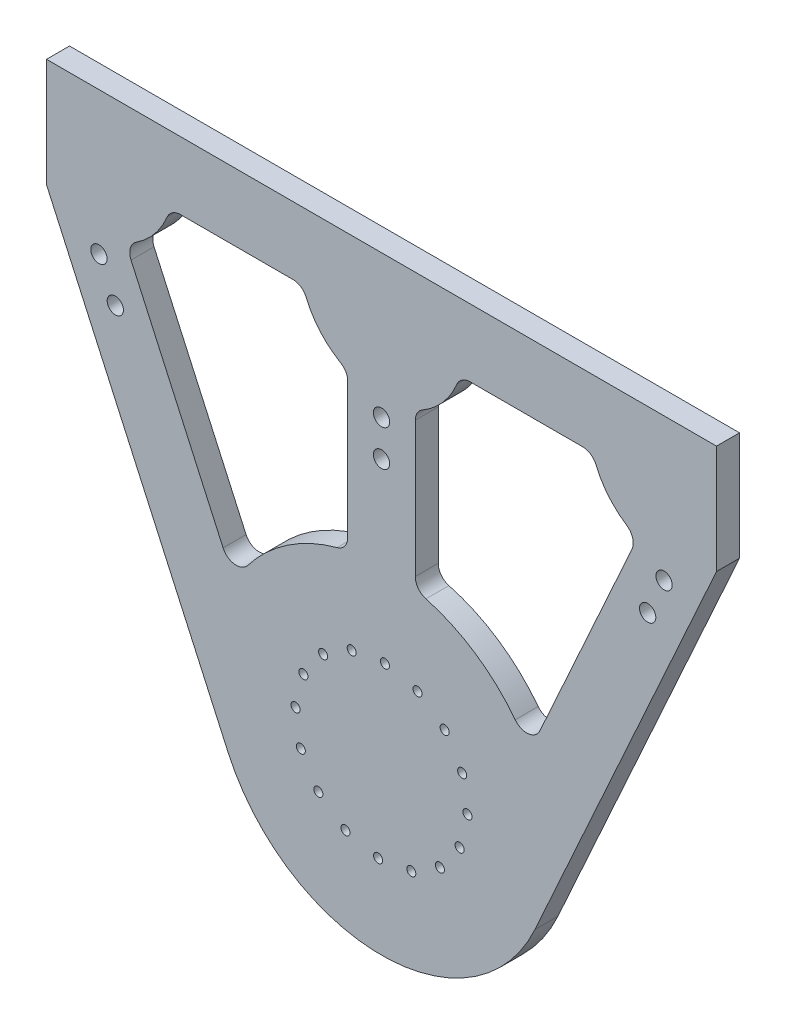
SolidWorks part; units mm, degrees
ref_plane "Front Plane" through (0, 0, 0) normal (0, 0, 1) x (1, 0, 0)
ref_plane "Top Plane" through (0, 0, 0) normal (0, 1, 0) x (1, 0, 0)
ref_plane "Right Plane" through (0, 0, 0) normal (1, 0, 0) x (0, 0, -1)
sketch "Sketch1" plane through (0, 0, 0) normal (0, 0, 1) x (1, 0, 0)
  line L1 (92.5, 121.5) -> (-92.5, 121.5)
  line L3 (0, 0) -> (0, 121.5) construction
  line L4 (-92.5, 121.5) -> (-92.5, 91.5)
  line L5 (-92.5, 91.5) -> (-42.3564, -19.1882)
  line L6 (92.5, 121.5) -> (92.5, 91.5)
  line L7 (92.5, 91.5) -> (42.3564, -19.1882)
  line L8 (42.3564, -19.1882) -> (-42.3564, -19.1882) construction
  circle A0 centre (0, 0) radius 46.5 construction
  arc A1 (-42.3564, -19.1882) -> (42.3564, -19.1882) centre (0, 0) ccw
  dimension "D1" = 93
  dimension "D2" = 185
  dimension "D3" = 121.5
  dimension "D4" = 30
extrude "Boss-Extrude1" add sketch "Sketch1" along normal mid plane 6.35
sketch "Sketch3" plane through (0, 0, -3.175) normal (0, 0, -1) x (-1, 0, 0)
  circle A0 centre (17.4402, -16.1215) radius 1.25 construction
  circle A1 centre (22.282, -8.2203) radius 1.25 construction
  circle A2 centre (9.9432, -21.5684) radius 1.25 construction
  circle A3 centre (0.9324, -23.7317) radius 1.25 construction
  circle A4 centre (-8.2203, -22.282) radius 1.25 construction
  circle A5 centre (-16.1215, -17.4402) radius 1.25 construction
  circle A6 centre (-21.5684, -9.9432) radius 1.25 construction
  circle A7 centre (-23.7317, -0.9324) radius 1.25 construction
  circle A8 centre (-22.282, 8.2203) radius 1.25 construction
  circle A9 centre (-17.4402, 16.1215) radius 1.25 construction
  circle A10 centre (-9.9432, 21.5684) radius 1.25 construction
  circle A11 centre (-0.9324, 23.7317) radius 1.25 construction
  circle A12 centre (8.2203, 22.282) radius 1.25 construction
  circle A13 centre (16.1215, 17.4402) radius 1.25 construction
  circle A14 centre (21.5684, 9.9432) radius 1.25 construction
  circle A15 centre (23.7317, 0.9324) radius 1.25 construction
  circle A16 centre (17.4402, -16.1215) radius 1.25
  circle A17 centre (22.282, -8.2203) radius 1.25
  circle A18 centre (9.9432, -21.5684) radius 1.25
  circle A19 centre (0.9324, -23.7317) radius 1.25
  circle A20 centre (-8.2203, -22.282) radius 1.25
  circle A21 centre (-16.1215, -17.4402) radius 1.25
  circle A22 centre (-21.5684, -9.9432) radius 1.25
  circle A23 centre (-23.7317, -0.9324) radius 1.25
  circle A24 centre (-22.282, 8.2203) radius 1.25
  circle A25 centre (-17.4402, 16.1215) radius 1.25
  circle A26 centre (-9.9432, 21.5684) radius 1.25
  circle A27 centre (-0.9324, 23.7317) radius 1.25
  circle A28 centre (8.2203, 22.282) radius 1.25
  circle A29 centre (16.1215, 17.4402) radius 1.25
  circle A30 centre (21.5684, 9.9432) radius 1.25
  circle A31 centre (23.7317, 0.9324) radius 1.25
extrude "Cut-Extrude2" cut sketch "Sketch3" against normal through all both and the other way through all
ref_plane "Plane1" through (0, 91.5, 0) normal (0, 1, 0) x (1, 0, 0)
ref_plane "Plane2" through (0, 106.5, 0) normal (0, 1, 0) x (1, 0, 0)
sketch "Sketch6" plane through (0, 0, -3.175) normal (0, 0, -1) x (-1, 0, 0)
  line L0 (0, 0) -> (0, 121.5) construction
  line L1 (-92.5, 121.5) -> (-77.5, 121.5) construction
  line L2 (-92.5, 121.5) -> (-92.5, 91.5) construction
  line L3 (-92.5, 91.5) -> (-77.5, 91.5) construction
  line L4 (-77.5, 121.5) -> (-77.5, 91.5) construction
  line L5 (-92.5, 121.5) -> (92.5, 121.5) construction
  line L6 (-85, 121.5) -> (-85, 106.5) construction
  line L11 (-77.5, 106.5) -> (-92.5, 106.5) construction
  line L12 (-7.5, 121.5) -> (7.5, 121.5) construction
  line L13 (-7.5, 121.5) -> (-7.5, 91.5) construction
  line L14 (-7.5, 91.5) -> (7.5, 91.5) construction
  line L15 (7.5, 121.5) -> (7.5, 91.5) construction
  line L16 (-85, 91.5) -> (-85, 106.5) construction
  circle A0 centre (-85, 114) radius 2.25
  circle A1 centre (-85, 99) radius 2.25
  circle A2 centre (0, 114) radius 2.25
  circle A3 centre (0, 99) radius 2.25
  circle A6 centre (85, 114) radius 2.25
  circle A7 centre (85, 99) radius 2.25
  point P18 (0, 121.5)
  point P35 (-85, 114)
  point P38 (-85, 99)
  dimension "D3" = 4.5
  dimension "D1" = 30
  dimension "D2" = 15
sketch "Sketch12" plane through (0, 0, -3.175) normal (0, 0, -1) x (-1, 0, 0)
  line L0 (0, -46.5) -> (0, 121.5) construction
  line L1 (-92.5, 121.5) -> (92.5, 121.5) construction
  line L2 (-87, 116) -> (-92.5, 116) construction
  line L3 (-87, 116) -> (-73, 116) construction
  line L4 (-87, 116) -> (-87, 102) construction
  line L5 (-87, 102) -> (-73, 102) construction
  line L6 (-73, 116) -> (-73, 102) construction
  line L7 (-92.5, 91.5) -> (-92.5, 121.5) construction
  line L8 (-87, 116) -> (-87, 121.5) construction
  line L9 (12.5, 121.5) -> (-12.5, 121.5) construction
  line L11 (-7, 102) -> (7, 102) construction
  line L12 (-7, 102) -> (-7, 116) construction
  line L13 (-7, 116) -> (7, 116) construction
  line L14 (7, 102) -> (7, 116) construction
  circle A0 centre (-7, 102) radius 2.25
  circle A2 centre (7, 102) radius 2.25
  circle A4 centre (7, 116) radius 2.25
  circle A5 centre (-87, 116) radius 2.25
  circle A6 centre (-73, 116) radius 2.25
  circle A7 centre (-73, 102) radius 2.25
  circle A8 centre (-87, 102) radius 2.25
  arc A9 (-42.3564, -19.1882) -> (42.3564, -19.1882) centre (0, 0) ccw construction
  circle A10 centre (87, 102) radius 2.25
  circle A11 centre (73, 102) radius 2.25
  circle A12 centre (73, 116) radius 2.25
  circle A13 centre (87, 116) radius 2.25
  circle A14 centre (-7, 116) radius 2.25
  point P22 (-87, 109)
  point P23 (-7, 109)
  point P24 (0, 116)
  dimension "D3" = 4.5
  dimension "D1" = 5.5
  dimension "D2" = 14
extrude "Cut-Extrude6" cut sketch "Sketch12" against normal through all both and the other way through all
sketch "Sketch13" plane through (0, 0, -3.175) normal (0, 0, -1) x (-1, 0, 0)
  line L0 (-40.7392, 22.418) -> (-70.6842, 88.5191)
  line L1 (40.7392, 22.418) -> (70.6842, 88.5191)
  line L2 (-9.3209, 88.5215) -> (-9.3209, 45.5562)
  line L3 (9.3209, 88.5215) -> (9.3209, 45.5562)
  line L7 (-7, 102) -> (7, 116) construction
  line L8 (-87, 102) -> (-73, 116) construction
  line L9 (58.3545, 102.8582) -> (21.6455, 102.8582)
  line L10 (-58.3545, 102.8582) -> (-21.6455, 102.8582)
  line L11 (25.3758, -11.4957) -> (73.8582, 95.5256)
  line L12 (73.8582, 95.5256) -> (73.8582, 102.8582)
  line L13 (73.8582, 102.8582) -> (-73.8582, 102.8582)
  line L14 (-73.8582, 102.8582) -> (-73.8582, 95.5256)
  line L15 (-73.8582, 95.5256) -> (-25.3758, -11.4957)
  line L16 (25.3758, -11.4957) -> (73.8582, 95.5256) construction
  line L17 (73.8582, 95.5256) -> (73.8582, 102.8582) construction
  line L18 (73.8582, 102.8582) -> (-73.8582, 102.8582) construction
  line L19 (-73.8582, 102.8582) -> (-73.8582, 95.5256) construction
  line L20 (-73.8582, 95.5256) -> (-25.3758, -11.4957) construction
  line L23 (0, 0) -> (0, 109) construction
  arc A0 (-40.7392, 22.418) -> (40.7392, 22.418) centre (0, 0) cw construction
  circle A1 centre (0, 0) radius 27.8582 construction
  arc A2 (-25.3758, -11.4957) -> (25.3758, -11.4957) centre (0, 0) ccw
  arc A3 (-25.3758, -11.4957) -> (25.3758, -11.4957) centre (0, 0) ccw construction
  circle A4 centre (7, 116) radius 2.25 construction
  circle A5 centre (-7, 102) radius 2.25 construction
  circle A6 centre (-73, 116) radius 2.25 construction
  circle A7 centre (-87, 102) radius 2.25 construction
  circle A8 centre (7, 116) radius 2.25 construction
  circle A9 centre (-7, 102) radius 2.25 construction
  circle A10 centre (-73, 116) radius 2.25 construction
  circle A11 centre (-87, 102) radius 2.25 construction
  circle A12 centre (-80, 109) radius 22.5 construction
  circle A13 centre (0, 109) radius 22.5 construction
  circle A14 centre (80, 109) radius 22.5 construction
  arc A15 (-70.6842, 88.5191) -> (-58.3545, 102.8582) centre (-80, 109) ccw
  arc A17 (58.3545, 102.8582) -> (70.6842, 88.5191) centre (80, 109) ccw
  arc A21 (-21.6455, 102.8582) -> (-9.3209, 88.5215) centre (0, 109) ccw
  arc A22 (9.3209, 88.5215) -> (21.6455, 102.8582) centre (0, 109) ccw
  arc A23 (-40.7392, 22.418) -> (-9.3209, 45.5562) centre (0, 0) cw
  arc A24 (9.3209, 45.5562) -> (40.7392, 22.418) centre (0, 0) cw
  dimension "D2" = 45
  dimension "D3" = 18.6418
  dimension "D4" = 46.5
  dimension "D1" = 18.6418
extrude "Cut-Extrude7" cut sketch "Sketch13" against normal through all both and the other way through all
fillet "Fillet4" radius 4 12 edges at (9.3209, 88.5215, 0) (9.3209, 45.5562, 0) (40.7392, 22.418, 0) (-70.6842, 88.5191, 0) (-40.7392, 22.418, 0) (-9.3209, 45.5562, 0) (-9.3209, 88.5215, 0) (-21.6455, 102.8582, 0) (-58.3545, 102.8582, 0) (21.6455, 102.8582, 0) (58.3545, 102.8582, 0) (70.6842, 88.5191, 0)
sketch "Sketch16" plane through (0, 0, 3.175) normal (0, 0, 1) x (1, 0, 0)
  circle A0 centre (-87, 102) radius 2.25 construction
  circle A1 centre (-87, 116) radius 2.25 construction
  circle A2 centre (-73, 116) radius 2.25 construction
  circle A3 centre (-73, 102) radius 2.25 construction
  circle A4 centre (-7, 116) radius 2.25 construction
  circle A5 centre (7, 116) radius 2.25 construction
  circle A6 centre (-7, 102) radius 2.25 construction
  circle A7 centre (7, 102) radius 2.25 construction
  circle A8 centre (73, 102) radius 2.25 construction
  circle A9 centre (87, 102) radius 2.25 construction
  circle A10 centre (73, 116) radius 2.25 construction
  circle A11 centre (87, 116) radius 2.25 construction
  circle A12 centre (-87, 102) radius 2.25
  circle A13 centre (-87, 116) radius 2.25
  circle A14 centre (-73, 116) radius 2.25
  circle A15 centre (-73, 102) radius 2.25
  circle A16 centre (-7, 116) radius 2.25
  circle A17 centre (7, 116) radius 2.25
  circle A18 centre (-7, 102) radius 2.25
  circle A19 centre (7, 102) radius 2.25
  circle A20 centre (73, 102) radius 2.25
  circle A21 centre (87, 102) radius 2.25
  circle A22 centre (73, 116) radius 2.25
  circle A23 centre (87, 116) radius 2.25
extrude "Boss-Extrude2" add sketch "Sketch16" against normal up to surface (6.35 mm away) up to face at (-35.1048, 75.6796, -3.175)
sketch "Sketch17" plane through (0, 0, -3.175) normal (0, 0, -1) x (-1, 0, 0)
  line L0 (0, 82.133) -> (78.0239, 82.133) construction
  line L1 (78.0239, 82.133) -> (73.4937, 72.133) construction
  line L2 (86.1416, 77.4644) -> (69.161, 85.1569) construction
  line L3 (92.5, 91.5) -> (42.3564, -19.1882) construction
  line L4 (69.161, 85.1569) -> (43.7423, 29.047) construction
  line L5 (-9.3209, 72.133) -> (9.3209, 72.133) construction
  line L6 (-9.3209, 86.0914) -> (-9.3209, 48.7114) construction
  line L7 (9.3209, 48.7114) -> (9.3209, 86.0914) construction
  line L8 (0, 82.133) -> (0, 72.133) construction
  line L9 (-92.5, 121.5) -> (92.5, 121.5) construction
  circle A0 centre (78.0239, 82.133) radius 2.25
  circle A1 centre (73.4937, 72.133) radius 2.25
  circle A2 centre (0, 82.133) radius 2.25
  circle A3 centre (0, 72.133) radius 2.25
  circle A4 centre (-73.4937, 72.133) radius 2.25
  circle A5 centre (-78.0239, 82.133) radius 2.25
  point P15 (0, 72.133)
  point P24 (77.6513, 81.3107)
  dimension "D1" = 4.5
  dimension "D2" = 10
  dimension "D3" = 39.367
extrude "Cut-Extrude8" cut sketch "Sketch17" against normal through all both and the other way through all
